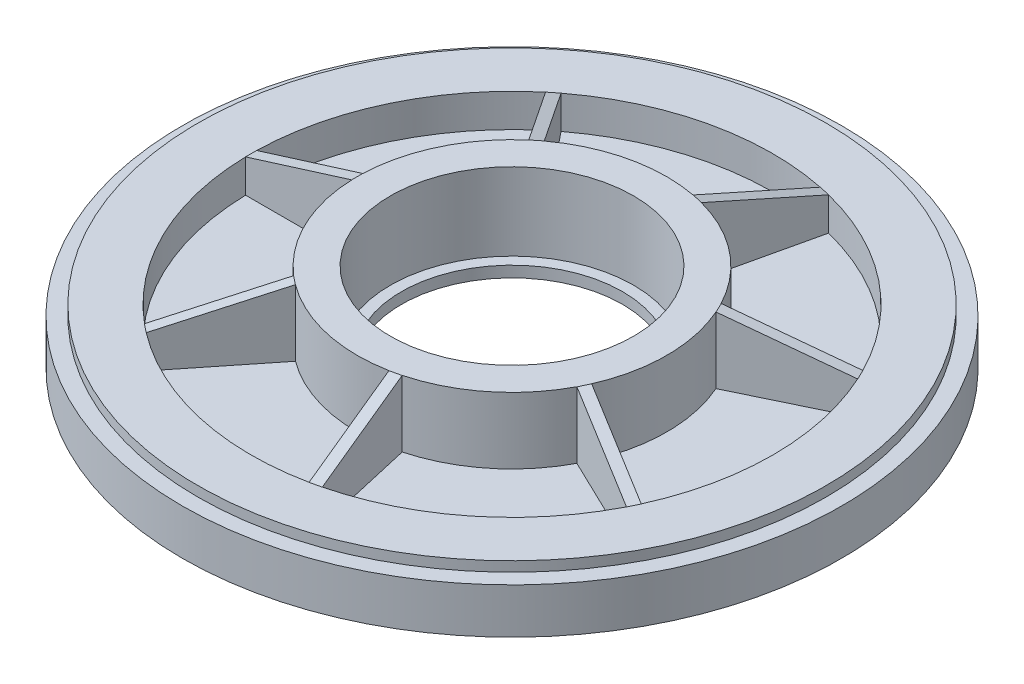
SolidWorks part; units mm, degrees
ref_plane "Front Plane" through (0, 0, 0) normal (0, 0, 1) x (1, 0, 0)
ref_plane "Top Plane" through (0, 0, 0) normal (0, 1, 0) x (1, 0, 0)
ref_plane "Right Plane" through (0, 0, 0) normal (1, 0, 0) x (0, 0, -1)
sketch "Sketch1" plane through (0, 0, 0) normal (0, 0, 1) x (1, 0, 0)
  line L0 (0, 0) -> (0, 11342.0758) construction
  line L1 (-11, 1) -> (-11, 8)
  line L2 (-11, 8) -> (-14, 8)
  line L3 (-12, 7) -> (-12, 0)
  line L4 (-14, 2) -> (-23.6, 2)
  line L5 (-23.6, 2) -> (-23.6, 5)
  line L6 (-23.6, 5) -> (-28.405, 5)
  line L7 (-28.405, 5) -> (-28.405, 4)
  line L8 (-28.405, 4) -> (-25.6, 4)
  line L9 (-25.6, 4) -> (-25.6, 0)
  line L11 (-10, 0) -> (-10, 1)
  line L12 (-10, 1) -> (-11, 1)
  line L14 (-12, 0) -> (-10, 0)
  line L16 (-25.6, 0) -> (-13, 0)
  line L17 (-14, 2) -> (-14, 8)
  line L19 (-12, 7) -> (-13, 7)
  line L20 (-13, 7) -> (-13, 0)
  point P7 (0, 0)
  point P8 (-12, -0.8139)
  point P19 (-28.405, 4.5)
  point P20 (0, 0)
  point P21 (-12, 0)
  point P24 (-16.0449, 8)
  point P25 (0, 0)
  point P27 (-27.0899, 0)
  dimension "D1" = 1
  dimension "D2" = 7
  dimension "D3" = 1
  dimension "D4" = 3
  dimension "D5" = 1
  dimension "D6" = 51.2
  dimension "D7" = 4
  dimension "D8" = 2
  dimension "D9" = 56.81
  dimension "D10" = 22
  dimension "D11" = 1
  dimension "D12" = 2
  dimension "D13" = 1
  dimension "D14" = 1
  dimension "D15" = 1
revolve "Revolve1" add sketch "Sketch1" angle 360 about L0
sketch "Sketch2" plane through (0, 0, 0) normal (0, 0, 1) x (1, 0, 0)
  line L0 (-14, 8) -> (-23.6, 5)
  line L1 (-23.6, 5) -> (-23.6, 2) construction
  line L2 (-23.6, 2) -> (-14, 2)
  line L3 (-14, 2) -> (-14, 8) construction
  line L4 (14, 2) -> (-14, 2) construction
  line L5 (23.6, 5) -> (-23.6, 5) construction
  line L6 (28.405, 5) -> (-28.405, 5) construction
  line L7 (-13.5, 2) -> (-13.5, 8)
  line L9 (-24.1, 5) -> (-24.1, 2)
  line L11 (-13.5, 8.6801) -> (-24.1, 5.3676) construction
  line L12 (-23.6, 5) -> (-24.1, 5)
  line L13 (-14, 8) -> (-13.5, 8)
  line L14 (-23.6, 2) -> (-24.1, 2)
  line L15 (-13.5, 1.5) -> (-13.5, 8.6801) construction
  line L16 (-24.1, 5.3676) -> (-24.1, 1.5) construction
  line L17 (-14, 2) -> (-13.5, 2)
  line L18 (-24.1, 1.5) -> (-13.5, 1.5) construction
  point P15 (0, 0)
  dimension "D1" = 0.5
extrude "Boss-Extrude1" add sketch "Sketch2" along normal blind 0.5 and the other way blind 0.5
ref_axis "Axis1" through (0, 8, 0) along (0, -1, 0)
pattern_circular "CirPattern1" count 7 over 360 about axis through (0, 8, 0) along (0, -1, 0) of "Boss-Extrude1"
fillet "Fillet2" 2 edges at (0, 7, -12) (0, 7, -13) type full round first side face at (0, 0, -12) second side face at (0, 7, -13) middle face at (0, 7, -12)
sketch "Sketch3" plane through (0, 0, 0) normal (0, 1, 0) x (1, 0, 0)
  circle A0 centre (0, 0) radius 29.405
  circle A1 centre (0, 0) radius 29.805
  circle A2 centre (0, 0) radius 28.405
  circle A3 centre (0, 0) radius 28.405 construction
  dimension "D1" = 1
  dimension "D2" = 0.4
extrude "Boss-Extrude2" add sketch "Sketch3" along direction (0, 1, 0) on the side of the normal up to surface (4 mm away) separate body contours A1 A0 region at (-29.7207, 0, 0) up to face at (0, 4, -25.6)
extrude "Boss-Extrude3" add sketch "Sketch3<3>" along normal blind 0.1 from surface contours A0 A2 | A1 A0 region at (-28.5733, 0, 0) region at (-29.7207, 0, 0) starting at face at (0, 4, 29.405)
sketch "Sketch3<3>" plane through (0, 0, 0) normal (0, 1, 0) x (1, 0, 0) same geometry as "Sketch3"
